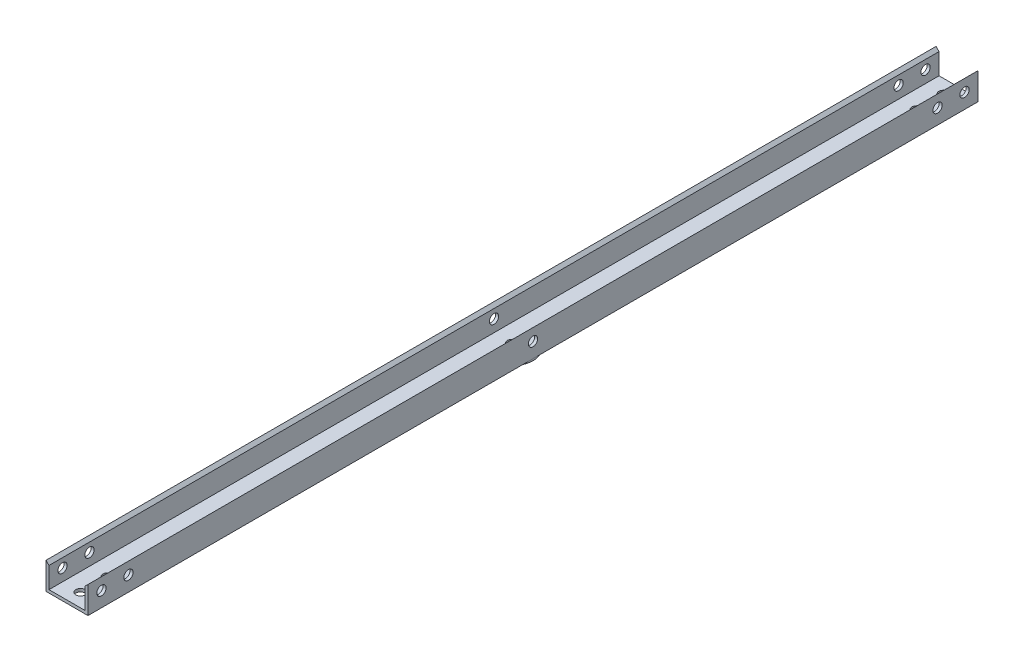
SolidWorks part; units mm, degrees
ref_plane "前视基准面" through (0, 0, 0) normal (0, 0, 1) x (1, 0, 0)
ref_plane "上视基准面" through (0, 0, 0) normal (0, 1, 0) x (1, 0, 0)
ref_plane "右视基准面" through (0, 0, 0) normal (1, 0, 0) x (0, 0, -1)
sketch "草图1" plane through (0, 0, 0) normal (0, 0, 1) x (1, 0, 0)
  line L0 (0, 0) -> (-97.4859, 0) construction
  line L2 (-70, 0) -> (-70, 85)
  line L3 (-70, 85) -> (-60, 85)
  line L4 (-60, 85) -> (-60, 5)
  line L5 (-60, 5) -> (60, 5)
  line L6 (60, 5) -> (60, 85)
  line L7 (60, 85) -> (70, 85)
  line L8 (70, 85) -> (70, -5)
  line L9 (70, -5) -> (-70, -5)
  line L10 (-70, -5) -> (-70, 0)
  line L11 (0, 0) -> (0, 76.9596) construction
  dimension "D1" = 10
  dimension "D2" = 10
  dimension "D3" = 140
  dimension "D4" = 90
extrude "拉伸1" add sketch "草图1" along normal mid plane 2970
chamfer "倒角1" distance 10 angle 45 2 edges at (60, 85, 0) (-60, 85, 0)
sketch "草图2" plane through (70, 0, 0) normal (1, 0, 0) x (0, 0, -1)
  line L0 (-1485, -5) -> (1485, -5) construction
  line L1 (-1485, -5) -> (-1485, 85) construction
  line L3 (1485, -5) -> (1485, 85) construction
  circle A0 centre (-1440, 45) radius 15.5
  circle A1 centre (-1350, 45) radius 15.5
  circle A2 centre (0, 45) radius 15.5
  circle A3 centre (1350, 45) radius 15.5
  circle A4 centre (1440, 45) radius 15.5
  point P14 (1485, 40)
  dimension "D1" = 31
  dimension "D2" = 50
  dimension "D3" = 45
  dimension "D4" = 90
  dimension "D5" = 1350
  dimension "D6" = 1350
  dimension "D7" = 90
  dimension "D8" = 45
extrude "拉伸2" cut sketch "草图2" against normal through all
sketch "草图4" plane through (0, -5, 0) normal (0, -1, 0) x (1, 0, 0)
  circle A0 centre (0, 0) radius 70
  dimension "D1" = 140
extrude "拉伸4" add sketch "草图4" along normal blind 6
sketch "草图3" plane through (0, -5, 0) normal (0, -1, 0) x (1, 0, 0)
  line L1 (-671.138, 0) -> (672.6708, 0) construction
  line L2 (-70, -1485) -> (70, -1485) construction
  line L4 (70, 1485) -> (70, 0) construction
  circle A0 centre (0, -1440) radius 15.5
  circle A1 centre (0, 0) radius 15.5
  circle A2 centre (0, -1350) radius 15.5
  circle A3 centre (0, 1350) radius 15.5
  circle A4 centre (0, 1440) radius 15.5
  point P7 (0, -1485)
  dimension "D1" = 31
  dimension "D2" = 45
  dimension "D3" = 70
  dimension "D6" = 31
  dimension "D7" = 31
  dimension "D4" = 90
  dimension "D5" = 1350
extrude "拉伸3" cut sketch "草图3" against normal through all and the other way through all
